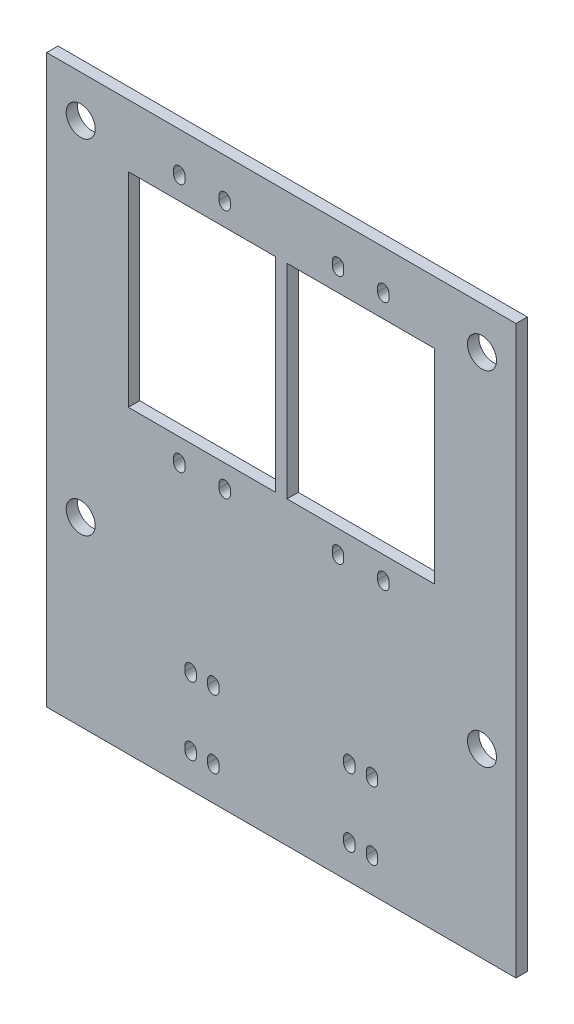
SolidWorks part; units mm, degrees
ref_plane "Front Plane" through (0, 0, 0) normal (0, 0, 1) x (1, 0, 0)
ref_plane "Top Plane" through (0, 0, 0) normal (0, 1, 0) x (1, 0, 0)
ref_plane "Right Plane" through (0, 0, 0) normal (1, 0, 0) x (0, 0, -1)
sketch "Sketch1" plane through (0, 0, 0) normal (0, 0, 1) x (1, 0, 0)
  line L1 (-131.445, 158.75) -> (131.445, 158.75)
  line L2 (-131.445, 158.75) -> (-131.445, -158.75)
  line L3 (-131.445, -158.75) -> (131.445, -158.75)
  line L4 (131.445, 158.75) -> (131.445, -158.75)
  line L5 (-131.445, 158.75) -> (131.445, -158.75) construction
  line L6 (-131.445, -158.75) -> (131.445, 158.75) construction
  point P0 (0, 0)
  dimension "D1" = 262.89
  dimension "D2" = 317.5
extrude "Boss-Extrude1" add sketch "Sketch1" along normal blind 6.35
sketch "Sketch2" plane through (0, 0, 6.35) normal (0, 0, 1) x (1, 0, 0)
  line L0 (0, 158.75) -> (0, -158.75) construction
  line L1 (-131.445, -158.75) -> (131.445, -158.75) construction
  line L2 (-112.395, 158.75) -> (-112.395, -158.75) construction
  line L3 (131.445, 158.75) -> (-131.445, 158.75) construction
  line L4 (-131.445, 158.75) -> (-131.445, -158.75) construction
  line L5 (-44.45, -139.7) -> (44.45, -139.7) construction
  line L6 (-50.8, -102.87) -> (-50.8, -100.33) construction
  line L7 (-38.1, -139.7) -> (-50.8, -139.7) construction
  line L8 (38.1, -139.7) -> (50.8, -139.7)
  line L9 (-44.45, -139.7) -> (-44.45, -101.6) construction
  line L10 (44.45, -139.7) -> (44.45, -101.6) construction
  line L11 (-50.8, -101.6) -> (-38.1, -101.6) construction
  line L12 (-53.975, -102.87) -> (-53.975, -100.33)
  line L13 (-47.625, -102.87) -> (-47.625, -100.33)
  line L14 (-38.1, -102.87) -> (-38.1, -100.33) construction
  line L15 (-34.925, -102.87) -> (-34.925, -100.33)
  line L16 (-41.275, -102.87) -> (-41.275, -100.33)
  line L17 (-44.45, -120.65) -> (-39.3755, -120.65) construction
  line L18 (-38.1, -138.43) -> (-38.1, -140.97) construction
  line L19 (-34.925, -138.43) -> (-34.925, -140.97)
  line L20 (-41.275, -138.43) -> (-41.275, -140.97)
  line L21 (-50.8, -138.43) -> (-50.8, -140.97) construction
  line L22 (-53.975, -138.43) -> (-53.975, -140.97)
  line L23 (-47.625, -138.43) -> (-47.625, -140.97)
  line L24 (50.8, -138.43) -> (50.8, -140.97) construction
  line L25 (53.975, -138.43) -> (53.975, -140.97)
  line L26 (47.625, -138.43) -> (47.625, -140.97)
  line L27 (38.1, -138.43) -> (38.1, -140.97) construction
  line L28 (34.925, -138.43) -> (34.925, -140.97)
  line L29 (41.275, -138.43) -> (41.275, -140.97)
  line L30 (38.1, -102.87) -> (38.1, -100.33) construction
  line L31 (34.925, -102.87) -> (34.925, -100.33)
  line L32 (41.275, -102.87) -> (41.275, -100.33)
  line L33 (50.8, -102.87) -> (50.8, -100.33) construction
  line L34 (53.975, -102.87) -> (53.975, -100.33)
  line L35 (47.625, -102.87) -> (47.625, -100.33)
  line L36 (-44.45, -101.6) -> (-44.45, 158.75) construction
  line L37 (44.45, -101.6) -> (44.45, 158.75) construction
  line L38 (-44.45, -120.65) -> (-44.45, 9.525) construction
  line L39 (-85.725, 9.525) -> (-3.175, 9.525)
  line L40 (-85.725, 9.525) -> (-85.725, 123.825)
  line L41 (-85.725, 123.825) -> (-3.175, 123.825)
  line L42 (-3.175, 123.825) -> (-3.175, 9.525)
  line L43 (-44.45, 136.525) -> (-31.75, 136.525) construction
  line L44 (-85.725, 66.675) -> (-44.45, 66.675) construction
  line L45 (-31.75, 137.795) -> (-31.75, 135.255) construction
  line L46 (-28.575, 137.795) -> (-28.575, 135.255)
  line L47 (-34.925, 137.795) -> (-34.925, 135.255)
  line L48 (-57.15, 137.795) -> (-57.15, 135.255) construction
  line L49 (-60.325, 137.795) -> (-60.325, 135.255)
  line L50 (-53.975, 137.795) -> (-53.975, 135.255)
  line L51 (-31.75, -4.445) -> (-31.75, -1.905) construction
  line L52 (-28.575, -4.445) -> (-28.575, -1.905)
  line L53 (-34.925, -4.445) -> (-34.925, -1.905)
  line L54 (-57.15, -4.445) -> (-57.15, -1.905) construction
  line L55 (-60.325, -4.445) -> (-60.325, -1.905)
  line L56 (-53.975, -4.445) -> (-53.975, -1.905)
  line L57 (31.75, -4.445) -> (31.75, -1.905) construction
  line L58 (28.575, -4.445) -> (28.575, -1.905)
  line L59 (34.925, -4.445) -> (34.925, -1.905)
  line L60 (57.15, -4.445) -> (57.15, -1.905) construction
  line L61 (60.325, -4.445) -> (60.325, -1.905)
  line L62 (53.975, -4.445) -> (53.975, -1.905)
  line L63 (85.725, 9.525) -> (3.175, 9.525)
  line L64 (3.175, 123.825) -> (3.175, 9.525)
  line L65 (85.725, 123.825) -> (3.175, 123.825)
  line L66 (85.725, 9.525) -> (85.725, 123.825)
  line L67 (31.75, 137.795) -> (31.75, 135.255) construction
  line L68 (28.575, 137.795) -> (28.575, 135.255)
  line L69 (34.925, 137.795) -> (34.925, 135.255)
  line L70 (57.15, 137.795) -> (57.15, 135.255) construction
  line L71 (60.325, 137.795) -> (60.325, 135.255)
  line L72 (53.975, 137.795) -> (53.975, 135.255)
  circle A1 centre (-112.395, -57.15) radius 8.128
  circle A4 centre (112.395, -57.15) radius 8.128
  arc A6 (-53.975, -102.87) -> (-47.625, -102.87) centre (-50.8, -102.87) ccw
  arc A7 (-47.625, -100.33) -> (-53.975, -100.33) centre (-50.8, -100.33) ccw
  arc A8 (-34.925, -102.87) -> (-41.275, -102.87) centre (-38.1, -102.87) cw
  arc A9 (-41.275, -100.33) -> (-34.925, -100.33) centre (-38.1, -100.33) cw
  arc A10 (-34.925, -138.43) -> (-41.275, -138.43) centre (-38.1, -138.43) ccw
  arc A11 (-41.275, -140.97) -> (-34.925, -140.97) centre (-38.1, -140.97) ccw
  arc A12 (-53.975, -138.43) -> (-47.625, -138.43) centre (-50.8, -138.43) cw
  arc A13 (-47.625, -140.97) -> (-53.975, -140.97) centre (-50.8, -140.97) cw
  arc A14 (53.975, -138.43) -> (47.625, -138.43) centre (50.8, -138.43) ccw
  arc A15 (47.625, -140.97) -> (53.975, -140.97) centre (50.8, -140.97) ccw
  arc A16 (34.925, -138.43) -> (41.275, -138.43) centre (38.1, -138.43) cw
  arc A17 (41.275, -140.97) -> (34.925, -140.97) centre (38.1, -140.97) cw
  arc A18 (34.925, -102.87) -> (41.275, -102.87) centre (38.1, -102.87) ccw
  arc A19 (41.275, -100.33) -> (34.925, -100.33) centre (38.1, -100.33) ccw
  arc A20 (53.975, -102.87) -> (47.625, -102.87) centre (50.8, -102.87) cw
  arc A21 (47.625, -100.33) -> (53.975, -100.33) centre (50.8, -100.33) cw
  arc A23 (-28.575, 137.795) -> (-34.925, 137.795) centre (-31.75, 137.795) ccw
  arc A24 (-34.925, 135.255) -> (-28.575, 135.255) centre (-31.75, 135.255) ccw
  arc A25 (-60.325, 137.795) -> (-53.975, 137.795) centre (-57.15, 137.795) cw
  arc A26 (-53.975, 135.255) -> (-60.325, 135.255) centre (-57.15, 135.255) cw
  arc A27 (-28.575, -4.445) -> (-34.925, -4.445) centre (-31.75, -4.445) cw
  arc A28 (-34.925, -1.905) -> (-28.575, -1.905) centre (-31.75, -1.905) cw
  arc A29 (-60.325, -4.445) -> (-53.975, -4.445) centre (-57.15, -4.445) ccw
  arc A30 (-53.975, -1.905) -> (-60.325, -1.905) centre (-57.15, -1.905) ccw
  arc A31 (28.575, -4.445) -> (34.925, -4.445) centre (31.75, -4.445) ccw
  arc A32 (34.925, -1.905) -> (28.575, -1.905) centre (31.75, -1.905) ccw
  arc A33 (60.325, -4.445) -> (53.975, -4.445) centre (57.15, -4.445) cw
  arc A34 (53.975, -1.905) -> (60.325, -1.905) centre (57.15, -1.905) cw
  arc A35 (28.575, 137.795) -> (34.925, 137.795) centre (31.75, 137.795) cw
  arc A36 (34.925, 135.255) -> (28.575, 135.255) centre (31.75, 135.255) cw
  arc A37 (60.325, 137.795) -> (53.975, 137.795) centre (57.15, 137.795) ccw
  arc A38 (53.975, 135.255) -> (60.325, 135.255) centre (57.15, 135.255) ccw
  circle A39 centre (-112.395, 135.255) radius 8.128
  circle A40 centre (112.395, 135.255) radius 8.128
  point P6 (0, 0)
  point P19 (-31.75, 136.525)
  point P28 (0, -139.7)
  point P31 (-44.45, -139.7)
  point P34 (44.45, -139.7)
  point P39 (-44.45, -101.6)
  point P40 (-50.8, -101.6)
  point P47 (-38.1, -101.6)
  point P56 (-38.1, -139.7)
  point P63 (-50.8, -139.7)
  point P70 (50.8, -139.7)
  point P77 (38.1, -139.7)
  point P84 (38.1, -101.6)
  point P91 (50.8, -101.6)
  point P102 (-44.45, 9.525)
  point P109 (-57.15, 136.525)
  point P116 (-31.75, -3.175)
  point P123 (-57.15, -3.175)
  point P130 (31.75, -3.175)
  point P137 (57.15, -3.175)
  point P148 (31.75, 136.525)
  point P155 (57.15, 136.525)
  dimension "D2" = 12.7
  dimension "D3" = 16.256
  dimension "D4" = 12.7
  dimension "D12" = 3.175
  dimension "D5" = 2.54
  dimension "D6" = 3.175
  dimension "D17" = 101.6
  dimension "D1" = 19.05
  dimension "D7" = 19.05
  dimension "D8" = 88.9
  dimension "D9" = 12.7
  dimension "D10" = 12.7
  dimension "D11" = 38.1
  dimension "D13" = 2.54
  dimension "D14" = 130.175
  dimension "D15" = 82.55
  dimension "D16" = 114.3
  dimension "D18" = 19.05
extrude "Cut-Extrude2" cut sketch "Sketch2" against normal blind 6.35 contours L42 L41 L40 L39 | L63 L66 L65 L64 | A26 L50 A25 L49 | L47 A24 L46 A23 | A36 L69 A35 L68 | L72 A38 L71 A37 | L56 A30 L55 A29 | A28 L53 A27 L52 | L59 A32 L58 A31 | A34 L62 A33 L61 | L13 A7 L12 A6 | A9 L16 A8 L15 | A13 L23 A12 L22 | L20 A11 L19 A10 | A17 L29 A16 L28 | L26 A15 L25 A14 | A21 L35 A20 L34 | L32 A19 L31 A18 | A1 | A4 region at (47.7342, -139.065, 6.35) region at (41.1658, -140.335, 6.35) region at (-50.8, -101.6, 6.35) region at (-38.1, -101.6, 6.35) region at (-38.1, -139.7, 6.35) region at (-50.8, -139.7, 6.35) region at (38.1, -101.6, 6.35) region at (50.8, -101.6, 6.35) region at (-44.45, 66.675, 6.35) region at (-31.75, 136.525, 6.35) region at (-57.15, 136.525, 6.35) region at (-31.75, -3.175, 6.35) region at (-57.15, -3.175, 6.35) region at (31.75, -3.175, 6.35) region at (57.15, -3.175, 6.35) region at (44.45, 66.675, 6.35) region at (31.75, 136.525, 6.35) region at (57.15, 136.525, 6.35) region at (-112.395, -57.15, 6.35) region at (112.395, -57.15, 6.35)
extrude "Cut-Extrude4" cut sketch "Sketch2<5>" against normal through all contours A39 | A40 region at (-112.395, 135.255, 6.35) region at (112.395, 135.255, 6.35)
sketch "Sketch2<5>" plane through (0, 0, 6.35) normal (0, 0, 1) x (1, 0, 0) same geometry as "Sketch2"
